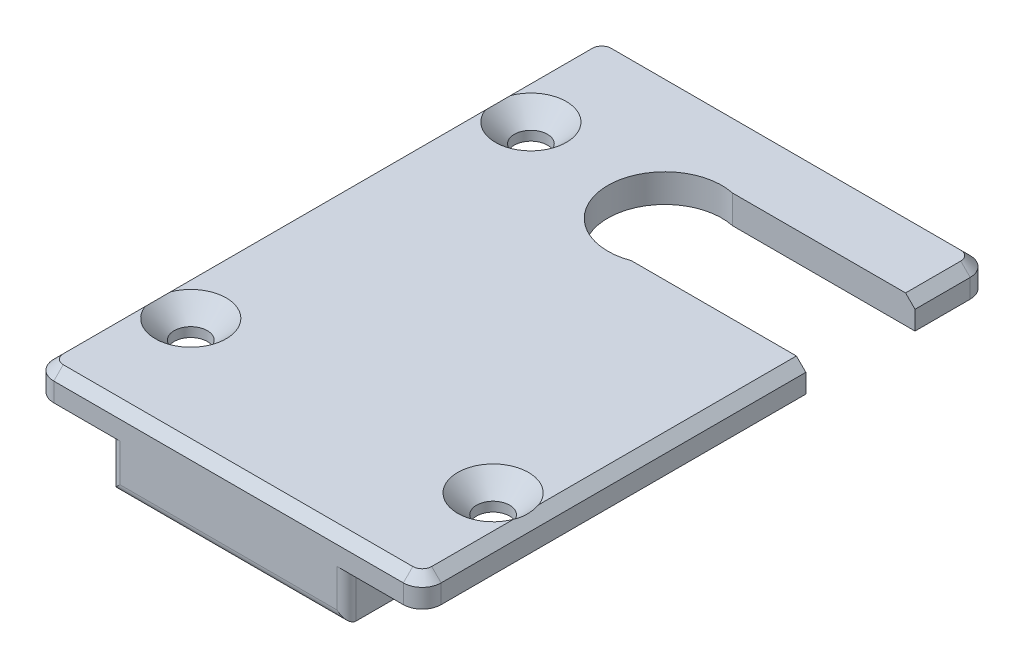
SolidWorks part; units mm, degrees
ref_plane "Спереди" through (0, 0, 0) normal (0, 0, 1) x (1, 0, 0)
ref_plane "Сверху" through (0, 0, 0) normal (0, 1, 0) x (1, 0, 0)
ref_plane "Справа" through (0, 0, 0) normal (1, 0, 0) x (0, 0, -1)
sketch "Эскиз1" plane through (0, 0, 0) normal (0, 1, 0) x (1, 0, 0)
  line L1 (-20.5, -30) -> (20.5, -30)
  line L2 (-20.5, -30) -> (-20.5, 30)
  line L3 (-20.5, 30) -> (20.5, 30)
  line L4 (20.5, -30) -> (20.5, 30)
  line L5 (0, 30) -> (0, -30) construction
  line L6 (-20.5, 0) -> (20.5, 0) construction
  point P0 (0, 0)
  dimension "D1" = 60
  dimension "D2" = 41
extrude "Бобышка-Вытянуть1" add sketch "Эскиз1" along normal blind 3
sketch "Эскиз2" plane through (0, 3, 0) normal (0, 1, 0) x (1, 0, 0)
  line L0 (0, 32.2776) -> (0, 0) construction
  line L1 (0, 0) -> (26.8846, 0) construction
  line L2 (20.5, -30) -> (20.5, 30) construction
  circle A0 centre (16, 18) radius 1.75
  circle A1 centre (16, -18) radius 1.75
  circle A2 centre (-16, -18) radius 1.75
  circle A3 centre (-16, 18) radius 1.75
  dimension "D1" = 18
  dimension "D2" = 4.5
  dimension "D3" = 3.5
extrude "Вырез-Вытянуть1" cut sketch "Эскиз2" against normal blind 3
fillet "Скругление1" radius 2 4 edges at (20.5, 1.5, -30) (-20.5, 1.5, -30) (-20.5, 1.5, 30) (20.5, 1.5, 30)
sketch "Эскиз3" plane through (0, 0, 0) normal (0, -1, 0) x (1, 0, 0)
  line L0 (0, 32.2375) -> (0, 0) construction
  line L1 (0, 0) -> (33.8614, 0) construction
  line L2 (-18.5, 30) -> (18.5, 30) construction
  line L3 (-12.5, 22) -> (12.5, 22)
  line L4 (-12.5, 22) -> (-12.5, 30)
  line L5 (-12.5, 30) -> (12.5, 30)
  line L6 (12.5, 22) -> (12.5, 30)
  line L7 (0, 30) -> (0, 22) construction
  line L8 (-12.5, 26) -> (12.5, 26) construction
  point P3 (0, 26)
  dimension "D1" = 25
  dimension "D2" = 8
extrude "Бобышка-Вытянуть2" add sketch "Эскиз3" along normal blind 5
fillet "Скругление2" radius 1 3 edges at (-12.5, -2.5, 30) (0, -5, 30) (12.5, -2.5, 30)
chamfer "Фаска2" distance 1 angle 45 8 edges at (-20.5, 3, 0) (19.9142, 3, -29.4142) (-19.9142, 3, -29.4142) (0, 3, -30) (-19.9142, 3, 29.4142) (0, 3, 30) (19.9142, 3, 29.4142) (20.5, 3, 0)
chamfer "Фаска1" distance 2 angle 45 4 edges at (-16, 3, 19.75) (16, 3, 16.25) (-16, 3, -19.75) (16, 3, -16.25)
sketch "Эскиз4" plane through (0, 3, 0) normal (0, 1, 0) x (1, 0, 0)
  line L0 (23.4186, 22.1575) -> (1.1874, 22.1575)
  line L1 (23.4186, 10.6017) -> (2.0235, 10.6017)
  line L2 (23.4186, 28.2171) -> (23.4186, 3.4703) construction
  line L3 (23.4186, 22.1575) -> (23.4186, 10.6017)
  arc A0 (1.1874, 22.1575) -> (2.0235, 10.6017) centre (-0.0813, 16.2575) ccw
  point P6 (25.716, 22.4318)
  point P7 (23.4186, 22.1575)
extrude "Вырез-Вытянуть3" cut sketch "Эскиз4" against normal blind 10
